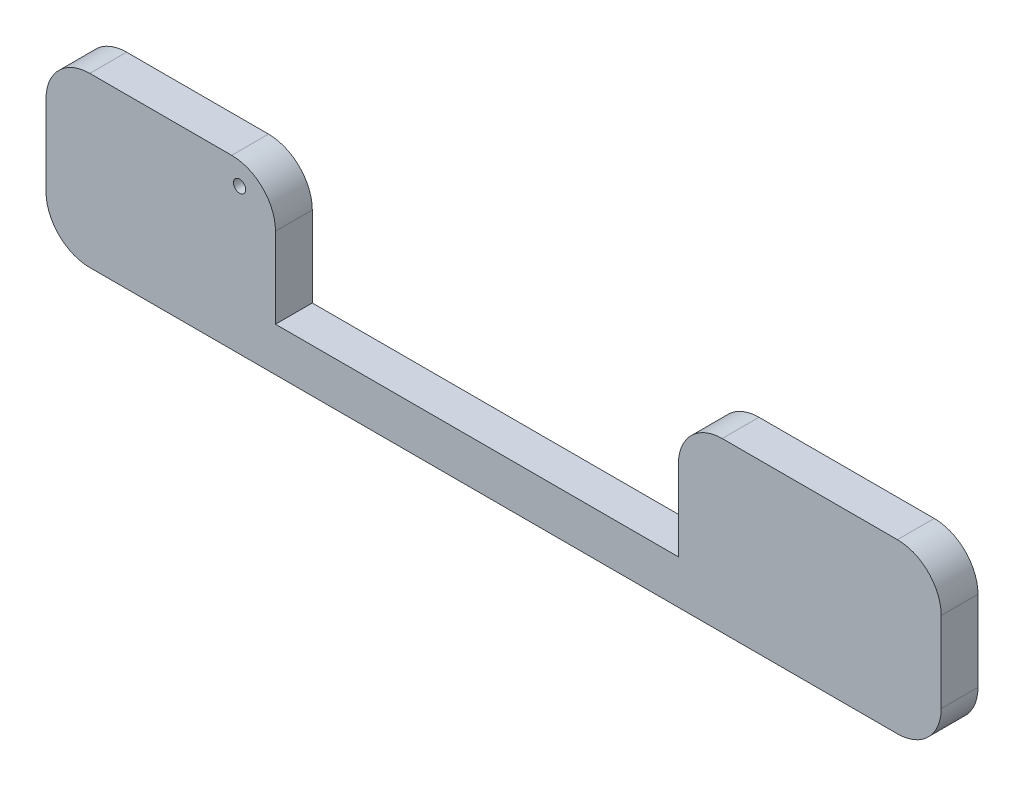
SolidWorks part; units mm, degrees
ref_plane "Front Plane" through (0, 0, 0) normal (0, 0, 1) x (1, 0, 0)
ref_plane "Top Plane" through (0, 0, 0) normal (0, 1, 0) x (1, 0, 0)
ref_plane "Right Plane" through (0, 0, 0) normal (1, 0, 0) x (0, 0, -1)
sketch "Sketch1" plane through (0, 0, 0) normal (0, 0, 1) x (1, 0, 0)
  line L1 (-85.0624, -35.0708) -> (44.7316, -35.0708)
  line L2 (-85.0624, -35.0708) -> (-85.0624, -59.4548)
  line L3 (-85.0624, -59.4548) -> (44.7316, -59.4548)
  line L4 (44.7316, -35.0708) -> (44.7316, -59.4548)
  dimension "D1" = 129.794
  dimension "D2" = 24.384
extrude "Boss-Extrude1" add sketch "Sketch1" along normal blind 5.334
sketch "Sketch3" plane through (0, 0, 5.334) normal (0, 0, 1) x (1, 0, 0)
  line L0 (44.7316, -35.0708) -> (-85.0624, -35.0708) construction
  line L1 (-51.7884, -35.0708) -> (6.6316, -35.0708)
  line L2 (-51.7884, -35.0708) -> (-51.7884, -53.1048)
  line L3 (-51.7884, -53.1048) -> (6.6316, -53.1048)
  line L4 (6.6316, -35.0708) -> (6.6316, -53.1048)
  line L5 (44.7316, -59.4548) -> (44.7316, -35.0708) construction
  dimension "D1" = 38.1
  dimension "D2" = 58.42
  dimension "D3" = 18.034
extrude "Cut-Extrude1" cut sketch "Sketch3" against normal through all
fillet "Fillet1" radius 6.35 6 edges at (-85.0624, -35.0708, 2.667) (-51.7884, -35.0708, 2.667) (6.6316, -35.0708, 2.667) (44.7316, -35.0708, 2.667) (44.7316, -59.4548, 2.667) (-85.0624, -59.4548, 2.667)
sketch "Sketch4" plane through (0, 0, 5.334) normal (0, 0, 1) x (1, 0, 0)
  line L1 (-85.0624, -47.2628) -> (-69.9279, -47.2628) construction
  line L2 (-85.0624, -41.4208) -> (-85.0624, -53.1048) construction
  line L3 (-68.4254, -35.0708) -> (-68.4254, -42.5901) construction
  line L4 (-58.1384, -35.0708) -> (-78.7124, -35.0708) construction
  circle A0 centre (-56.9954, -38.3728) radius 0.889
  dimension "D1" = 1.778
  dimension "D2" = 8.89
  dimension "D3" = 11.43
extrude "Cut-Extrude2" cut sketch "Sketch4" against normal through all
equation "\"MDF\"= .21in"
equation "\"Foamcore\"= .13in"
equation "\"Gmaterial\"= \"MDF\""
equation "\"D2@Sketch1\"=\"MDF\"+.25+.5"
equation "\"D1@Boss-Extrude1\"=\"MDF\""
equation "\"D3@Sketch3\"=\"MDF\"+.5"
